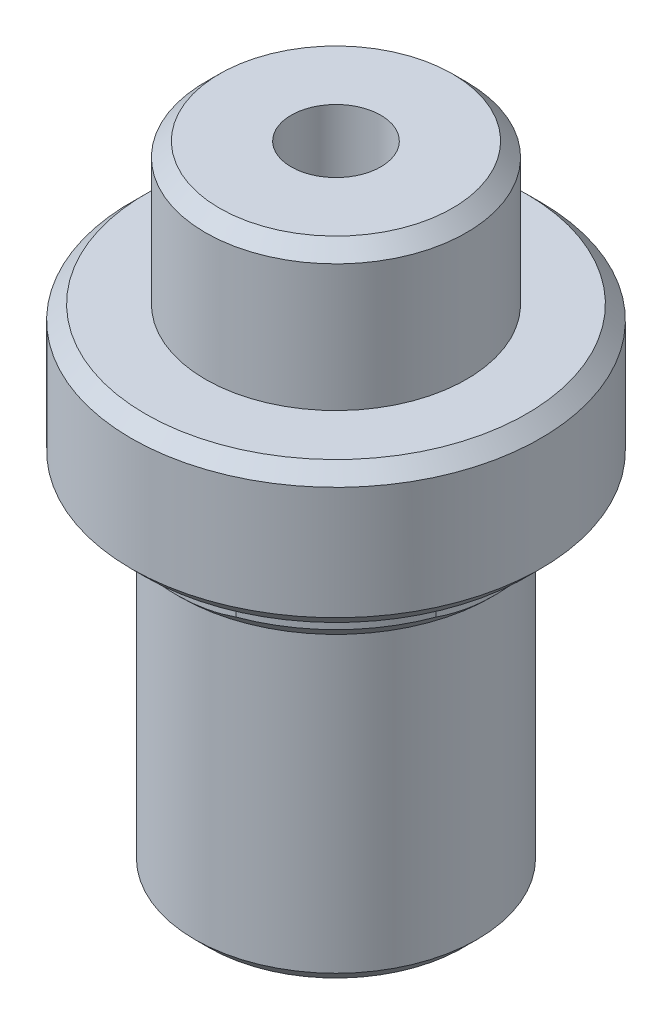
SolidWorks part; units mm, degrees
ref_plane "Front (X-Y)" through (0, 0, 0) normal (0, 0, 1) x (1, 0, 0)
ref_plane "Top (X-Z)" through (0, 0, 0) normal (0, 1, 0) x (1, 0, 0)
ref_plane "Right (Y-Z)" through (0, 0, 0) normal (1, 0, 0) x (0, 0, -1)
ref_axis "X-Axis" through (-88.99, 0, 0) along (1, 0, 0)
ref_axis "Y-Axis" through (0, 55, 0) along (0, -1, 0)
ref_axis "Z-Axis" through (0, 0, -88.99) along (0, 0, 1)
sketch "Sketch1" plane through (0, 0, 0) normal (0, 0, 1) x (1, 0, 0)
  line L0 (0, 38.2504) -> (0, -21.3457) construction
  line L1 (18.5, 0) -> (18.5, 20)
  line L2 (18.5, 20) -> (6.35, 20)
  line L3 (6.35, 20) -> (6.35, -70)
  line L4 (18.5, 0) -> (29, 0)
  line L5 (29, 0) -> (29, -20)
  line L6 (29, -20) -> (24, -20)
  line L7 (20, -25) -> (20, -70)
  line L8 (20, -70) -> (6.35, -70)
  line L9 (24, -20) -> (24, -25)
  line L10 (24, -25) -> (20, -25)
  dimension "D1" = 37
  dimension "D2" = 12.7
  dimension "D3" = 58
  dimension "D4" = 20
  dimension "D5" = 20
  dimension "D6" = 40
  dimension "D7" = 45
  dimension "D8" = 5
  dimension "D9" = 5
  dimension "D10" = 48
revolve "Revolve2" add sketch "Sketch1" angle 360 about L0
chamfer "Chamfer1" distance 2 angle 45 5 edges at (0, 20, 18.5) (0, 0, 29) (0, -70, 20) (0, -25, 24) (0, -20, 29)
sketch "Sketch2" plane through (0, -20, 0) normal (0, -1, 0) x (1, 0, 0)
  line L0 (22.5, 22.5) -> (22.5, -22.5)
  line L1 (0, 11.61) -> (0, -11.61) construction
  line L2 (-22.5, 22.5) -> (-22.5, -22.5)
  line L3 (22.5, 22.5) -> (-22.5, 22.5)
  line L4 (22.5, -22.5) -> (-22.5, -22.5)
  line L5 (0, 0) -> (22.5, 0) construction
  dimension "D1" = 45
  dimension "D2" = 45
  dimension "D3" = 22.5
  dimension "D4" = 22.5
extrude "Cut-Extrude1" cut sketch "Sketch2" along normal through all flip side to cut
